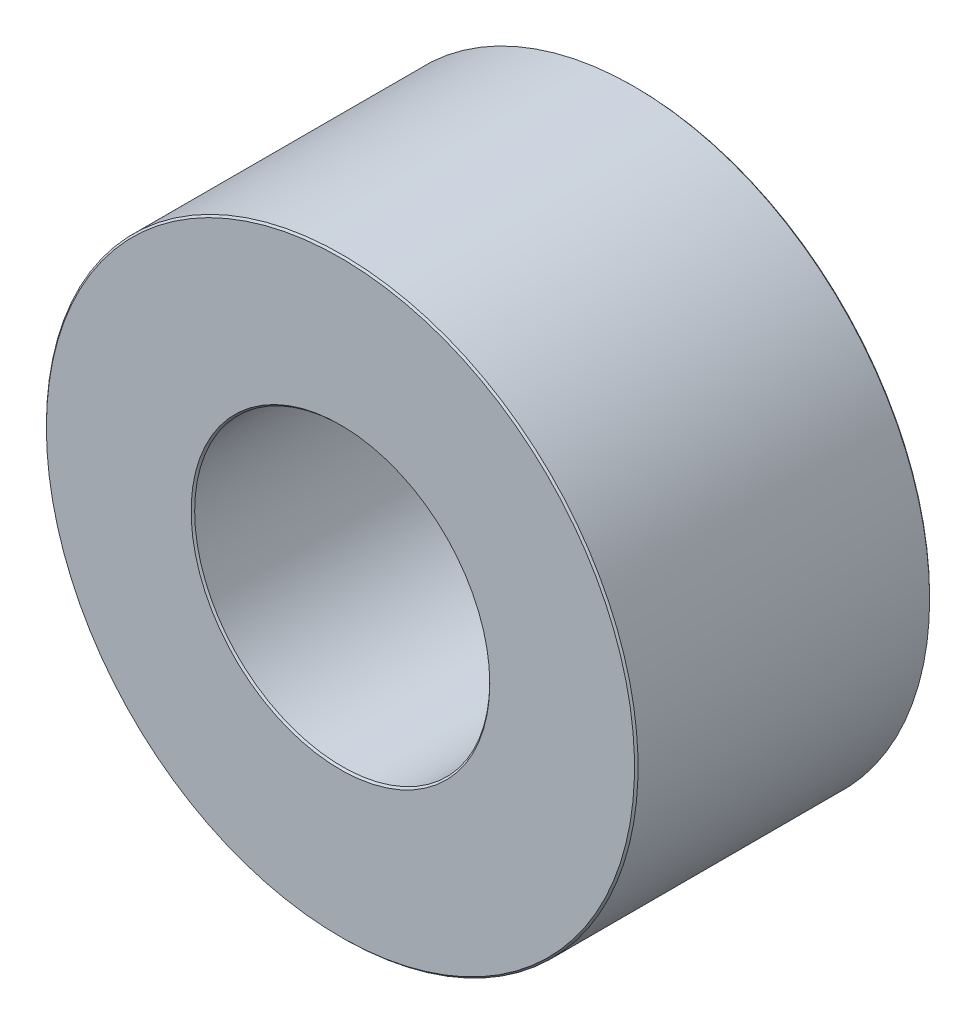
SolidWorks part; units mm, degrees
ref_plane "Front Plane" through (0, 0, 0) normal (0, 0, 1) x (1, 0, 0)
ref_plane "Top Plane" through (0, 0, 0) normal (0, 1, 0) x (1, 0, 0)
ref_plane "Right Plane" through (0, 0, 0) normal (1, 0, 0) x (0, 0, -1)
sketch "Sketch1" plane through (0, 0, 0) normal (0, 0, 1) x (1, 0, 0)
  circle A0 centre (0, 0) radius 6.015
  circle A1 centre (0, 0) radius 3
  point P8 (0, -6.015)
  point P9 (0, 6.015)
  dimension "ID" = 6
  dimension "OD" = 12.03
sketch "Sketch2" plane through (0, 0, 0) normal (1, 0, 0) x (0, 0, -1)
  line L0 (3, 0) -> (-3, 0) construction
  line L1 (3, 6.015) -> (-3, 6.015) construction
  point P4 (0, 0)
  point P8 (0, 6.015)
  point P9 (0, 6.015)
  dimension "Length" = 6
sketch "Sketch5" plane through (0, 0, 0) normal (0, 0, 1) x (1, 0, 0)
  circle A0 centre (0, 0) radius 3 construction
  circle A1 centre (0, 0) radius 6.015 construction
  circle A2 centre (0, 0) radius 3
  circle A3 centre (0, 0) radius 6.015
extrude "Boss-Extrude1" add sketch "Sketch5" along normal up to vertex and the other way up to vertex up to point (0, 0, 3) other way up to point (0, 0, -3)
chamfer "Chamfer1" distance 0.036 angle 45 4 edges at (6.015, 0, -3) (3, 0, -3) (3, 0, 3) (6.015, 0, 3)
equation "\"D1@Chamfer1\"=\"ID@Sketch1\"*.006"
